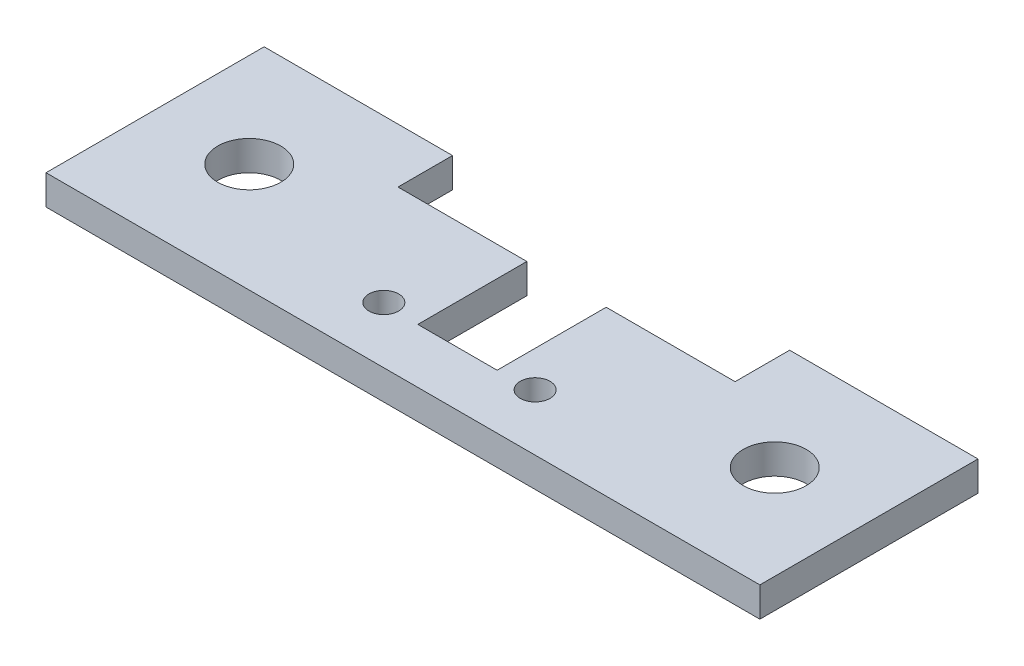
SolidWorks part; units mm, degrees
ref_plane "Front Plane" through (0, 0, 0) normal (0, 0, 1) x (1, 0, 0)
ref_plane "Top Plane" through (0, 0, 0) normal (0, 1, 0) x (1, 0, 0)
ref_plane "Right Plane" through (0, 0, 0) normal (1, 0, 0) x (0, 0, -1)
sketch "Sketch1" plane through (0, 0, 0) normal (0, 1, 0) x (1, 0, 0)
  line L0 (-4, 0) -> (-4, -5.5) construction
  line L1 (0, 0) -> (-8, 0)
  line L2 (0, 0) -> (0, -11)
  line L3 (0, -11) -> (-8, -11)
  line L4 (-8, 0) -> (-8, -11)
  line L5 (-21, 0) -> (13, 0)
  line L6 (-21, 0) -> (-21, -16.5)
  line L7 (-21, -16.5) -> (13, -16.5)
  line L8 (13, 0) -> (13, -16.5)
  line L9 (13, 5.5) -> (32, 5.5)
  line L10 (-21, -16.5) -> (13, 0) construction
  line L11 (-4, -5.5) -> (-4, -13.3) construction
  line L12 (-14.13, -13.3) -> (6.13, -13.3) construction
  line L13 (6.13, -13.3) -> (6.13, 2.3) construction
  line L14 (6.13, -13.3) -> (3.63, -13.3) construction
  line L15 (3.63, -13.3) -> (3.63, -10.8) construction
  line L16 (-4, -5.5) -> (6.13, -5.5) construction
  line L17 (-14.13, -13.3) -> (-14.13, 2.3) construction
  line L18 (-14.13, 2.3) -> (6.13, 2.3) construction
  line L19 (-4, -9.35) -> (-4, -17.6) construction
  line L20 (-21, -16.5) -> (-40, -16.5)
  line L21 (-21, -16.5) -> (-21, 5.5)
  line L22 (-21, 5.5) -> (-40, 5.5)
  line L23 (-40, -16.5) -> (-40, 5.5)
  line L24 (13, 0) -> (13, -16.5)
  line L25 (13, -16.5) -> (32, -16.5)
  line L26 (32, -16.5) -> (32, 5.5)
  line L27 (-30.5, -16.5) -> (-30.5, 5.5) construction
  line L28 (-40, -5.5) -> (-21, -5.5) construction
  line L29 (32, -5.5) -> (13, -5.5) construction
  line L30 (22.5, -16.5) -> (22.5, 5.5) construction
  line L31 (13, 0) -> (13, 5.5)
  circle A0 centre (3.63, -10.8) radius 1.5
  circle A1 centre (-11.63, -10.8) radius 1.5
  circle A2 centre (-30.5, -5.5) radius 3.175
  circle A3 centre (22.5, -5.5) radius 3.175
  point P28 (-14.13, -5.5)
  dimension "D10" = 3
  dimension "D4" = 6.35
  dimension "D1" = 8
  dimension "D2" = 11
  dimension "D3" = 34
  dimension "D5" = 5.5
  dimension "D6" = 7.8
  dimension "D7" = 10.13
  dimension "D8" = 2.5
  dimension "D9" = 2.5
  dimension "D11" = 16.5
  dimension "D12" = 19
  dimension "D13" = 22
  dimension "D14" = 19
  dimension "D15" = 11
extrude "Boss-Extrude1" add sketch "Sketch1" along normal blind 3 contours L8 L5 L2 L3 L4 L6 L7 A0 A1 | L23 L20 L6 L21 L22 A2 | L31 L8 L25 L26 L9 A3 region at (6.5, 0, 0.3779) region at (13.2907, 0, -2.75) region at (-21.2907, 0, 8.25)
